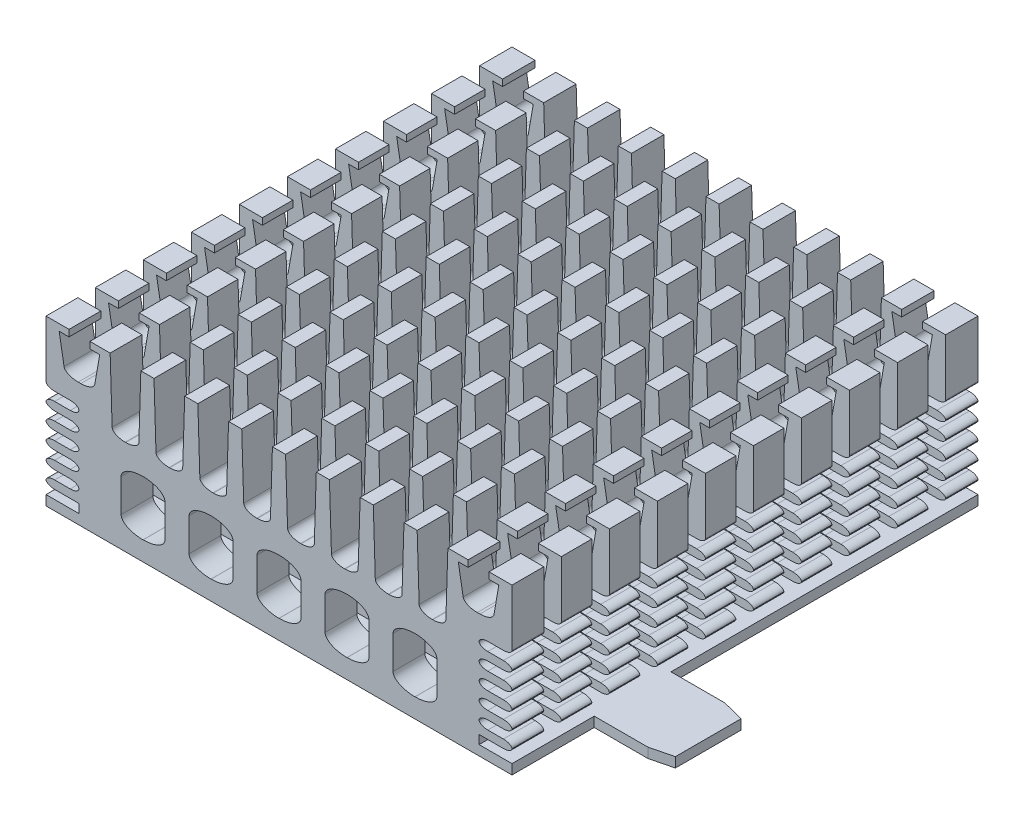
SolidWorks part; units mm, degrees
material "Aleación 1060"
ref_plane "Alzado" through (0, 0, 0) normal (0, 0, 1) x (1, 0, 0)
ref_plane "Planta" through (0, 0, 0) normal (0, 1, 0) x (1, 0, 0)
ref_plane "Vista lateral" through (0, 0, 0) normal (1, 0, 0) x (0, 0, -1)
sketch "Croquis3" plane through (0, 0, 0) normal (0, 1, 0) x (1, 0, 0)
  line L1 (-21.25, 21.25) -> (21.25, 21.25)
  line L2 (-21.25, 21.25) -> (-21.25, -21.25)
  line L3 (-21.25, -21.25) -> (21.25, -21.25)
  line L4 (21.25, 21.25) -> (21.25, -21.25)
  dimension "D1" = 42.5
  dimension "D2" = 42.5
  dimension "D3" = 21.25
  dimension "D4" = 21.25
extrude "Extruir1" add sketch "Croquis3" along normal blind 30
sketch "Croquis4" plane through (0, 0, 21.25) normal (0, 0, 1) x (1, 0, 0)
  line L0 (-19.15, 30) -> (-19.15, 28.8)
  line L1 (-21.25, 30) -> (21.25, 30) construction
  line L2 (-19.15, 28.8) -> (-20.05, 28.8)
  line L3 (-20.05, 28.8) -> (-19.6028, 23.6778)
  line L4 (-18.3177, 22.5) -> (-18.0823, 22.5)
  line L5 (-16.7972, 23.6778) -> (-16.35, 28.8)
  line L6 (-16.35, 28.8) -> (-17.25, 28.8)
  line L7 (-17.25, 28.8) -> (-17.25, 30)
  line L8 (-17.25, 30) -> (-19.15, 30)
  line L9 (-0.6, 30) -> (-0.7816, 18.4713)
  line L10 (-18.2, 30) -> (-18.2, 19.4356) construction
  line L11 (-21.25, 30) -> (-21.25, 0) construction
  line L12 (0, 30) -> (0, 39.1053) construction
  line L13 (-1.9714, 17.3) -> (-2.0286, 17.3)
  line L14 (17.25, 30) -> (19.15, 30)
  line L15 (17.25, 28.8) -> (17.25, 30)
  line L16 (16.35, 28.8) -> (17.25, 28.8)
  line L17 (16.7972, 23.6778) -> (16.35, 28.8)
  line L18 (18.3177, 22.5) -> (18.0823, 22.5)
  line L19 (20.05, 28.8) -> (19.6028, 23.6778)
  line L20 (19.15, 28.8) -> (20.05, 28.8)
  line L21 (19.15, 30) -> (19.15, 28.8)
  line L22 (-3.2184, 18.4713) -> (-3.4, 30)
  line L23 (-3.4, 30) -> (-0.6, 30)
  line L24 (-2, 30) -> (-2, 27.0397) construction
  line L25 (-4.6, 30) -> (-4.7816, 18.4713)
  line L26 (-5.9714, 17.3) -> (-6.0286, 17.3)
  line L27 (-7.2184, 18.4713) -> (-7.4, 30)
  line L28 (-7.4, 30) -> (-4.6, 30)
  line L29 (-6, 30) -> (-6, 27.0397) construction
  line L30 (-8.6, 30) -> (-8.7816, 18.4713)
  line L31 (-9.9714, 17.3) -> (-10.0286, 17.3)
  line L32 (-11.2184, 18.4713) -> (-11.4, 30)
  line L33 (-11.4, 30) -> (-8.6, 30)
  line L34 (-10, 30) -> (-10, 27.0397) construction
  line L35 (-12.6, 30) -> (-12.7816, 18.4713)
  line L36 (-13.9714, 17.3) -> (-14.0286, 17.3)
  line L37 (-15.2184, 18.4713) -> (-15.4, 30)
  line L38 (-15.4, 30) -> (-12.6, 30)
  line L39 (-14, 30) -> (-14, 27.0397) construction
  line L40 (14, 30) -> (14, 27.0397) construction
  line L41 (10, 30) -> (10, 27.0397) construction
  line L42 (6, 30) -> (6, 27.0397) construction
  line L43 (2, 30) -> (2, 27.0397) construction
  line L44 (15.4, 30) -> (12.6, 30)
  line L45 (15.2184, 18.4713) -> (15.4, 30)
  line L46 (13.9714, 17.3) -> (14.0286, 17.3)
  line L47 (12.6, 30) -> (12.7816, 18.4713)
  line L48 (11.4, 30) -> (8.6, 30)
  line L49 (11.2184, 18.4713) -> (11.4, 30)
  line L50 (9.9714, 17.3) -> (10.0286, 17.3)
  line L51 (8.6, 30) -> (8.7816, 18.4713)
  line L52 (7.4, 30) -> (4.6, 30)
  line L53 (7.2184, 18.4713) -> (7.4, 30)
  line L54 (5.9714, 17.3) -> (6.0286, 17.3)
  line L55 (4.6, 30) -> (4.7816, 18.4713)
  line L56 (3.4, 30) -> (0.6, 30)
  line L57 (3.2184, 18.4713) -> (3.4, 30)
  line L58 (1.9714, 17.3) -> (2.0286, 17.3)
  line L59 (0.6, 30) -> (0.7816, 18.4713)
  arc A0 (-19.6028, 23.6778) -> (-18.3177, 22.5) centre (-18.3177, 23.79) ccw
  arc A1 (-18.0823, 22.5) -> (-16.7972, 23.6778) centre (-18.0823, 23.79) ccw
  arc A2 (18.0823, 22.5) -> (16.7972, 23.6778) centre (18.0823, 23.79) cw
  arc A3 (19.6028, 23.6778) -> (18.3177, 22.5) centre (18.3177, 23.79) cw
  arc A4 (-0.7816, 18.4713) -> (-1.9714, 17.3) centre (-1.9714, 18.49) cw
  arc A5 (-2.0286, 17.3) -> (-3.2184, 18.4713) centre (-2.0286, 18.49) cw
  arc A6 (-4.7816, 18.4713) -> (-5.9714, 17.3) centre (-5.9714, 18.49) cw
  arc A7 (-6.0286, 17.3) -> (-7.2184, 18.4713) centre (-6.0286, 18.49) cw
  arc A8 (-8.7816, 18.4713) -> (-9.9714, 17.3) centre (-9.9714, 18.49) cw
  arc A9 (-10.0286, 17.3) -> (-11.2184, 18.4713) centre (-10.0286, 18.49) cw
  arc A10 (-12.7816, 18.4713) -> (-13.9714, 17.3) centre (-13.9714, 18.49) cw
  arc A11 (-14.0286, 17.3) -> (-15.2184, 18.4713) centre (-14.0286, 18.49) cw
  arc A12 (14.0286, 17.3) -> (15.2184, 18.4713) centre (14.0286, 18.49) ccw
  arc A13 (12.7816, 18.4713) -> (13.9714, 17.3) centre (13.9714, 18.49) ccw
  arc A14 (10.0286, 17.3) -> (11.2184, 18.4713) centre (10.0286, 18.49) ccw
  arc A15 (8.7816, 18.4713) -> (9.9714, 17.3) centre (9.9714, 18.49) ccw
  arc A16 (6.0286, 17.3) -> (7.2184, 18.4713) centre (6.0286, 18.49) ccw
  arc A17 (4.7816, 18.4713) -> (5.9714, 17.3) centre (5.9714, 18.49) ccw
  arc A18 (2.0286, 17.3) -> (3.2184, 18.4713) centre (2.0286, 18.49) ccw
  arc A19 (0.7816, 18.4713) -> (1.9714, 17.3) centre (1.9714, 18.49) ccw
  point P17 (-19.5, 22.5)
  point P20 (-16.9, 22.5)
  point P37 (16.9, 22.5)
  point P38 (19.5, 22.5)
  point P45 (-0.8, 17.3)
  point P48 (-3.2, 17.3)
  point P119 (3.2, 17.3)
  point P120 (0.8, 17.3)
  dimension "D9" = 1.29
  dimension "D15" = 1.19
  dimension "D1" = 1.9
  dimension "D2" = 3.7
  dimension "D3" = 1.85
  dimension "D4" = 1.2
  dimension "D5" = 7.5
  dimension "D6" = 2.6
  dimension "D7" = 1.3
  dimension "D8" = 2.1
  dimension "D10" = 2.8
  dimension "D11" = 2.4
  dimension "D12" = 1.2
  dimension "D13" = 12.7
  dimension "D14" = 0.6
extrude "Cortar-Extruir1" cut sketch "Croquis4" against normal blind 55
sketch "Croquis5" plane through (0, 0, 21.25) normal (0, 0, 1) x (1, 0, 0)
  line L0 (-21.25, 30) -> (-21.25, 0) construction
  line L1 (-21.8997, 18.9) -> (-18.25, 18.9)
  line L2 (-21.8997, 18.9) -> (-21.8997, 17.3)
  line L3 (-21.8997, 17.3) -> (-18.25, 17.3)
  line L4 (-18.25, 18.9) -> (-18.25, 17.3)
  line L5 (-21.8997, 15.8) -> (-18.25, 15.8)
  line L6 (-21.8997, 15.8) -> (-21.8997, 14.2)
  line L7 (-21.8997, 14.2) -> (-18.25, 14.2)
  line L8 (-18.25, 15.8) -> (-18.25, 14.2)
  line L9 (-21.8997, 12.7) -> (-18.25, 12.7)
  line L10 (-21.8997, 12.7) -> (-21.8997, 11.1)
  line L11 (-21.8997, 11.1) -> (-18.25, 11.1)
  line L12 (-18.25, 12.7) -> (-18.25, 11.1)
  line L13 (-21.8997, 9.6) -> (-18.25, 9.6)
  line L14 (-21.8997, 9.6) -> (-21.8997, 8)
  line L15 (-21.8997, 8) -> (-18.25, 8)
  line L16 (-18.25, 9.6) -> (-18.25, 8)
  line L17 (-21.8997, 6.5) -> (-18.25, 6.5)
  line L18 (-21.8997, 6.5) -> (-21.8997, 4.9)
  line L19 (-21.8997, 4.9) -> (-18.25, 4.9)
  line L20 (-18.25, 6.5) -> (-18.25, 4.9)
  line L21 (-21.8997, 3.4) -> (-18.25, 3.4)
  line L22 (-21.8997, 3.4) -> (-21.8997, 1.8)
  line L23 (-21.8997, 1.8) -> (-18.25, 1.8)
  line L24 (-18.25, 3.4) -> (-18.25, 1.8)
  line L25 (0, 0) -> (0, -4.9995) construction
  line L26 (18.25, 3.4) -> (18.25, 1.8)
  line L27 (21.8997, 1.8) -> (18.25, 1.8)
  line L28 (21.8997, 3.4) -> (21.8997, 1.8)
  line L29 (21.8997, 3.4) -> (18.25, 3.4)
  line L30 (18.25, 6.5) -> (18.25, 4.9)
  line L31 (21.8997, 4.9) -> (18.25, 4.9)
  line L32 (21.8997, 6.5) -> (21.8997, 4.9)
  line L33 (21.8997, 6.5) -> (18.25, 6.5)
  line L34 (18.25, 9.6) -> (18.25, 8)
  line L35 (21.8997, 8) -> (18.25, 8)
  line L36 (21.8997, 9.6) -> (21.8997, 8)
  line L37 (21.8997, 9.6) -> (18.25, 9.6)
  line L38 (18.25, 12.7) -> (18.25, 11.1)
  line L39 (21.8997, 11.1) -> (18.25, 11.1)
  line L40 (21.8997, 12.7) -> (21.8997, 11.1)
  line L41 (21.8997, 12.7) -> (18.25, 12.7)
  line L42 (18.25, 15.8) -> (18.25, 14.2)
  line L43 (21.8997, 14.2) -> (18.25, 14.2)
  line L44 (21.8997, 15.8) -> (21.8997, 14.2)
  line L45 (21.8997, 15.8) -> (18.25, 15.8)
  line L46 (18.25, 18.9) -> (18.25, 17.3)
  line L47 (21.8997, 17.3) -> (18.25, 17.3)
  line L48 (21.8997, 18.9) -> (21.8997, 17.3)
  line L49 (21.8997, 18.9) -> (18.25, 18.9)
  dimension "D1" = 3
  dimension "D2" = 1.6
  dimension "D3" = 1.5
extrude "Cortar-Extruir2" cut sketch "Croquis5" against normal blind 55
fillet "Redondeo1" radius 0.79 21 edges at (-21.25, 3.4, 0) (-21.25, 4.9, 0) (-18.25, 4.9, 0) (-18.25, 6.5, 0) (-21.25, 6.5, 0) (-21.25, 8, 0) (-18.25, 9.6, 0) (-18.25, 8, 0) (-21.25, 9.6, 0) (-21.25, 11.1, 0) (-18.25, 12.7, 0) (-18.25, 11.1, 0) (-21.25, 12.7, 0) (-21.25, 14.2, 0) (-18.25, 14.2, 0) (-18.25, 15.8, 0) (-21.25, 15.8, 0) (-21.25, 17.3, 0) (-21.25, 18.9, 0) (-18.25, 17.3, 0) (-18.25, 18.9, 0)
fillet "Redondeo2" radius 0.79 21 edges at (21.25, 3.4, 0) (21.25, 4.9, 0) (18.25, 4.9, 0) (18.25, 6.5, 0) (21.25, 6.5, 0) (21.25, 8, 0) (18.25, 8, 0) (18.25, 9.6, 0) (21.25, 9.6, 0) (21.25, 11.1, 0) (18.25, 11.1, 0) (18.25, 12.7, 0) (21.25, 12.7, 0) (21.25, 14.2, 0) (18.25, 14.2, 0) (18.25, 15.8, 0) (21.25, 15.8, 0) (21.25, 17.3, 0) (18.25, 17.3, 0) (18.25, 18.9, 0) (21.25, 18.9, 0)
sketch "Croquis7" plane through (0, 0, 21.25) normal (0, 0, 1) x (1, 0, 0)
  line L0 (0, 0) -> (0, -2.1081) construction
  line L1 (-0.01, 13.5) -> (0.01, 13.5)
  line L2 (-2, 11.51) -> (-2, 5.49)
  line L3 (-0.01, 3.5) -> (0.01, 3.5)
  line L4 (2, 11.51) -> (2, 5.49)
  line L5 (-21.25, 0) -> (21.25, 0) construction
  line L6 (6.19, 13.5) -> (6.21, 13.5)
  line L7 (4.2, 11.51) -> (4.2, 5.49)
  line L8 (6.19, 3.5) -> (6.21, 3.5)
  line L9 (8.2, 11.51) -> (8.2, 5.49)
  line L10 (12.39, 13.5) -> (12.41, 13.5)
  line L11 (10.4, 11.51) -> (10.4, 5.49)
  line L12 (12.39, 3.5) -> (12.41, 3.5)
  line L13 (14.4, 11.51) -> (14.4, 5.49)
  line L14 (-14.4, 11.51) -> (-14.4, 5.49)
  line L15 (-12.39, 3.5) -> (-12.41, 3.5)
  line L16 (-10.4, 11.51) -> (-10.4, 5.49)
  line L17 (-12.39, 13.5) -> (-12.41, 13.5)
  line L18 (-8.2, 11.51) -> (-8.2, 5.49)
  line L19 (-6.19, 3.5) -> (-6.21, 3.5)
  line L20 (-4.2, 11.51) -> (-4.2, 5.49)
  line L21 (-6.19, 13.5) -> (-6.21, 13.5)
  arc A0 (0.01, 3.5) -> (2, 5.49) centre (0.01, 5.49) ccw
  arc A1 (-2, 5.49) -> (-0.01, 3.5) centre (-0.01, 5.49) ccw
  arc A2 (-0.01, 13.5) -> (-2, 11.51) centre (-0.01, 11.51) ccw
  arc A3 (0.01, 13.5) -> (2, 11.51) centre (0.01, 11.51) cw
  arc A4 (6.21, 3.5) -> (8.2, 5.49) centre (6.21, 5.49) ccw
  arc A5 (4.2, 5.49) -> (6.19, 3.5) centre (6.19, 5.49) ccw
  arc A6 (6.19, 13.5) -> (4.2, 11.51) centre (6.19, 11.51) ccw
  arc A7 (6.21, 13.5) -> (8.2, 11.51) centre (6.21, 11.51) cw
  arc A8 (12.41, 3.5) -> (14.4, 5.49) centre (12.41, 5.49) ccw
  arc A9 (10.4, 5.49) -> (12.39, 3.5) centre (12.39, 5.49) ccw
  arc A10 (12.39, 13.5) -> (10.4, 11.51) centre (12.39, 11.51) ccw
  arc A11 (12.41, 13.5) -> (14.4, 11.51) centre (12.41, 11.51) cw
  arc A12 (-12.41, 13.5) -> (-14.4, 11.51) centre (-12.41, 11.51) ccw
  arc A13 (-12.39, 13.5) -> (-10.4, 11.51) centre (-12.39, 11.51) cw
  arc A14 (-10.4, 5.49) -> (-12.39, 3.5) centre (-12.39, 5.49) cw
  arc A15 (-12.41, 3.5) -> (-14.4, 5.49) centre (-12.41, 5.49) cw
  arc A16 (-6.21, 13.5) -> (-8.2, 11.51) centre (-6.21, 11.51) ccw
  arc A17 (-6.19, 13.5) -> (-4.2, 11.51) centre (-6.19, 11.51) cw
  arc A18 (-4.2, 5.49) -> (-6.19, 3.5) centre (-6.19, 5.49) cw
  arc A19 (-6.21, 3.5) -> (-8.2, 5.49) centre (-6.21, 5.49) cw
  dimension "D5" = 1.99
  dimension "D1" = 10
  dimension "D2" = 4
  dimension "D3" = 2
  dimension "D4" = 3.5
extrude "Cortar-Extruir3" cut sketch "Croquis7" against normal blind 55
sketch "Croquis8" plane through (21.25, 0, 0) normal (1, 0, 0) x (0, 0, -1)
  line L0 (-21.25, 30) -> (-21.25, 19.69) construction
  line L1 (-18.35, 32.5522) -> (-16.75, 32.5522)
  line L2 (-18.35, 32.5522) -> (-18.35, 2.5)
  line L3 (-18.35, 2.5) -> (-16.75, 2.5)
  line L4 (-16.75, 32.5522) -> (-16.75, 2.5)
  line L5 (-21.25, 0) -> (21.25, 0) construction
  line L6 (-13.97, 32.5522) -> (-12.37, 32.5522)
  line L7 (-13.97, 32.5522) -> (-13.97, 2.5)
  line L8 (-13.97, 2.5) -> (-12.37, 2.5)
  line L9 (-12.37, 32.5522) -> (-12.37, 2.5)
  line L10 (-9.59, 32.5522) -> (-7.99, 32.5522)
  line L11 (-9.59, 32.5522) -> (-9.59, 2.5)
  line L12 (-9.59, 2.5) -> (-7.99, 2.5)
  line L13 (-7.99, 32.5522) -> (-7.99, 2.5)
  line L14 (-5.21, 32.5522) -> (-3.61, 32.5522)
  line L15 (-5.21, 32.5522) -> (-5.21, 2.5)
  line L16 (-5.21, 2.5) -> (-3.61, 2.5)
  line L17 (-3.61, 32.5522) -> (-3.61, 2.5)
  line L18 (-0.83, 32.5522) -> (0.77, 32.5522)
  line L19 (-0.83, 32.5522) -> (-0.83, 2.5)
  line L20 (-0.83, 2.5) -> (0.77, 2.5)
  line L21 (0.77, 32.5522) -> (0.77, 2.5)
  line L22 (3.55, 32.5522) -> (5.15, 32.5522)
  line L23 (3.55, 32.5522) -> (3.55, 2.5)
  line L24 (3.55, 2.5) -> (5.15, 2.5)
  line L25 (5.15, 32.5522) -> (5.15, 2.5)
  line L26 (7.93, 32.5522) -> (9.53, 32.5522)
  line L27 (7.93, 32.5522) -> (7.93, 2.5)
  line L28 (7.93, 2.5) -> (9.53, 2.5)
  line L29 (9.53, 32.5522) -> (9.53, 2.5)
  line L30 (12.31, 32.5522) -> (13.91, 32.5522)
  line L31 (12.31, 32.5522) -> (12.31, 2.5)
  line L32 (12.31, 2.5) -> (13.91, 2.5)
  line L33 (13.91, 32.5522) -> (13.91, 2.5)
  line L34 (16.69, 32.5522) -> (18.29, 32.5522)
  line L35 (16.69, 32.5522) -> (16.69, 2.5)
  line L36 (16.69, 2.5) -> (18.29, 2.5)
  line L37 (18.29, 32.5522) -> (18.29, 2.5)
  dimension "D1" = 1.6
  dimension "D2" = 2.9
  dimension "D3" = 2.5
extrude "Cortar-Extruir4" cut sketch "Croquis8" against normal blind 55
sketch "Croquis9" plane through (0, 0, 0) normal (0, -1, 0) x (1, 0, 0)
  line L0 (-21.25, -12.31) -> (-21.25, -9.53) construction
  line L1 (-28.15, -13.75) -> (-21.25, -13.75)
  line L2 (-28.15, -13.75) -> (-28.15, -6.75)
  line L3 (-28.15, -6.75) -> (-21.25, -6.75)
  line L4 (-21.25, -13.75) -> (-21.25, -6.75)
  line L5 (21.25, -21.25) -> (21.25, 21.25) construction
  line L6 (21.25, 13.75) -> (28.15, 13.75)
  line L7 (21.25, 13.75) -> (21.25, 6.75)
  line L8 (21.25, 6.75) -> (28.15, 6.75)
  line L9 (28.15, 13.75) -> (28.15, 6.75)
  dimension "D1" = 7
  dimension "D2" = 6.9
  dimension "D3" = 7.5
  dimension "D4" = 7.5
  dimension "D5" = 7
  dimension "D6" = 6.9
extrude "Extruir2" add sketch "Croquis9" against normal blind 1.8
chamfer "Chaflán1" distance 0.5 angle 76 1 edges at (28.15, 0.9, 13.75) first distance on face at (28.15, 0.9, 10.25)
chamfer "Chaflán2" distance 0.5 angle 76 1 edges at (28.15, 0.9, 6.75) first distance on face at (28.15, 0.9, 10)
chamfer "Chaflán3" distance 0.5 angle 76 1 edges at (-28.15, 0.9, -6.75) first distance on face at (-28.15, 0.9, -10.25)
chamfer "Chaflán4" distance 0.5 angle 76 1 edges at (-28.15, 0.9, -13.75) first distance on face at (-28.15, 0.9, -10.5)
scale "Scale1" scale about centroid uniform scaling no x scale factor 0.5 y scale factor 0.25 z scale factor 0.5
